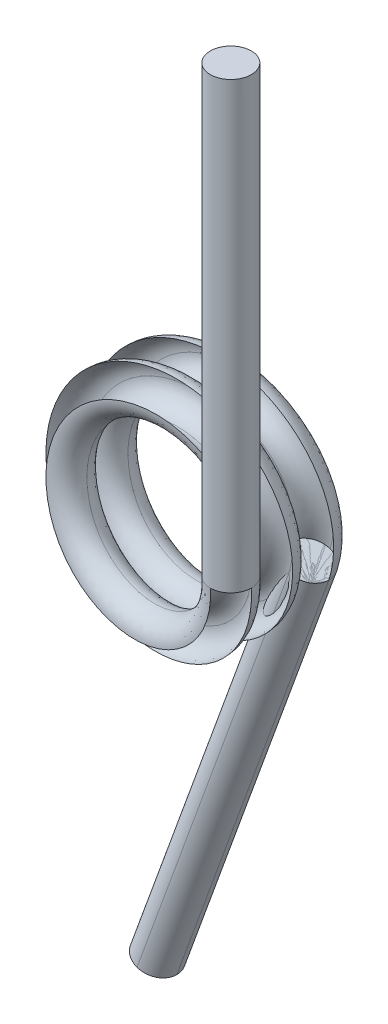
SolidWorks part; units mm, degrees
ref_plane "Front" through (0, 0, 0) normal (0, 0, 1) x (1, 0, 0)
ref_plane "Top" through (0, 0, 0) normal (0, 1, 0) x (1, 0, 0)
ref_plane "Right" through (0, 0, 0) normal (1, 0, 0) x (0, 0, -1)
sketch "Sketch1" plane through (0, 0, 0) normal (0, 0, 1) x (1, 0, 0)
  circle A0 centre (0, 0) radius 1.35
  circle A1 centre (0, 0) radius 1.05 construction
  circle A2 centre (0, 1.35) radius 0.3 construction
  dimension "D1" = 0.6
  dimension "D2" = 2.1
curve "Helix/Spiral1" pitch 0.6 height 1.2333 radius 1.35 centre (0, 0, 0) axis (0, 0, -1) start towards (1, 0, 0)
sketch "Sketch2" plane through (0, 0, 0) normal (0, 1, 0) x (1, 0, 0)
  circle A0 centre (1.35, 0) radius 0.3
  dimension "D1" = 0.6
sweep "Sweep1" add profiles "Sketch2" path "Helix/Spiral1"
sketch "Sketch4" plane through (0, 0, 0) normal (-0.342, -0.9397, 0) x (0, 0, -1)
  arc A0 (1.2328, 1.05) -> (1.533, 1.35) centre (1.2332, 1.3498) ccw
  arc A4 (1.2328, 1.05) -> (1.533, 1.35) centre (1.2332, 1.3498) ccw
  arc A24 (0.933, 1.35) -> (1.2328, 1.05) centre (1.2331, 1.3501) ccw
  arc A27 (1.533, 1.35) -> (1.2328, 1.65) centre (1.2332, 1.3502) ccw
  arc A28 (1.533, 1.35) -> (1.2328, 1.65) centre (1.2332, 1.3502) ccw
  arc A29 (1.2328, 1.65) -> (0.933, 1.35) centre (1.2332, 1.3498) ccw
  arc A30 (1.2328, 1.65) -> (0.933, 1.35) centre (1.2332, 1.3498) ccw
  arc A31 (0.933, 1.35) -> (1.2328, 1.05) centre (1.2331, 1.3501) ccw
  dimension "D1" = 0
extrude "Boss-Extrude1" add sketch "Sketch4" along normal blind 6.5 separate body
sketch "Sketch5" plane through (0, 0, 0) normal (0, 1, 0) x (1, 0, 0)
  arc A5 (1.35, 0.3) -> (1.05, 0) centre (1.35, 0) ccw
  arc A23 (1.35, 0.3) -> (1.05, 0) centre (1.35, 0) ccw
  arc A26 (1.65, 0) -> (1.35, 0.3) centre (1.35, 0) ccw
  arc A27 (1.65, 0) -> (1.35, 0.3) centre (1.35, 0) ccw
  arc A28 (1.05, 0) -> (1.35, -0.3) centre (1.35, 0) ccw
  arc A29 (1.05, 0) -> (1.35, -0.3) centre (1.35, 0) ccw
  arc A31 (1.35, -0.3) -> (1.65, 0) centre (1.35, 0) ccw
  arc A33 (1.35, -0.3) -> (1.65, 0) centre (1.35, 0) ccw
  dimension "D1" = 0
extrude "Boss-Extrude2" add sketch "Sketch5" along normal blind 6.5
ref_plane "Plane3" through (0, 0, -1) normal (0, 0, 1) x (1, 0, 0)
sketch "Sketch24" plane through (0, 0, -1) normal (0, 0, 1) x (1, 0, 0)
  circle A0 centre (0, 0) radius 3
